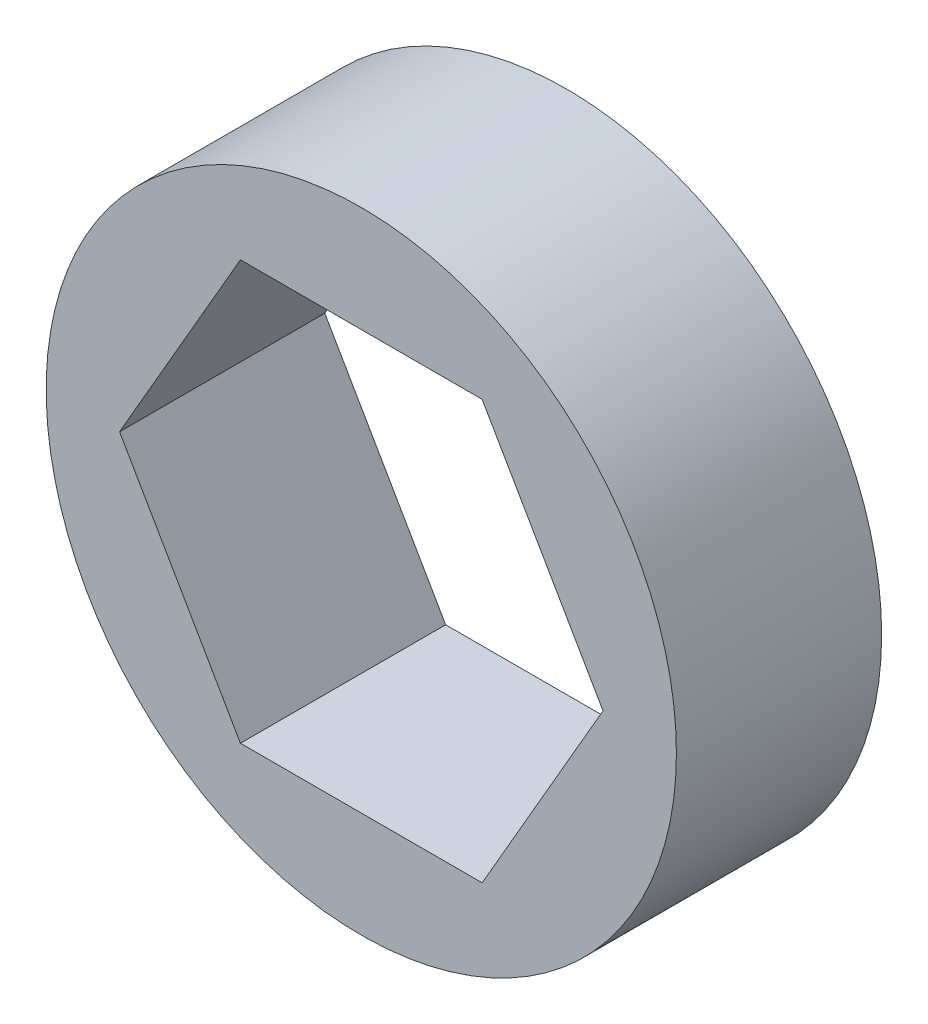
SolidWorks part; units mm, degrees
ref_plane "Front Plane" through (0, 0, 0) normal (0, 0, 1) x (1, 0, 0)
ref_plane "Top Plane" through (0, 0, 0) normal (0, 1, 0) x (1, 0, 0)
ref_plane "Right Plane" through (0, 0, 0) normal (1, 0, 0) x (0, 0, -1)
sketch "Sketch1" plane through (0, 0, 0) normal (0, 0, 1) x (1, 0, 0)
  line L0 (-3.7395, 6.477) -> (3.7395, 6.477)
  line L1 (3.7395, 6.477) -> (7.479, 0)
  line L2 (7.479, 0) -> (3.7395, -6.477)
  line L3 (3.7395, -6.477) -> (-3.7395, -6.477)
  line L4 (-3.7395, -6.477) -> (-7.479, 0)
  line L5 (-7.479, 0) -> (-3.7395, 6.477)
  circle A0 centre (0, 0) radius 9.75
  dimension "D1" = 19.5
  dimension "D2" = 3.7395
  dimension "D3" = 7.479
  dimension "D4" = 3.7395
extrude "Boss-Extrude1" add sketch "Sketch1" against normal mid plane 6.35
ref_axis "Axis1" through (0, 0, -3.175) along (0, 0, 1)
